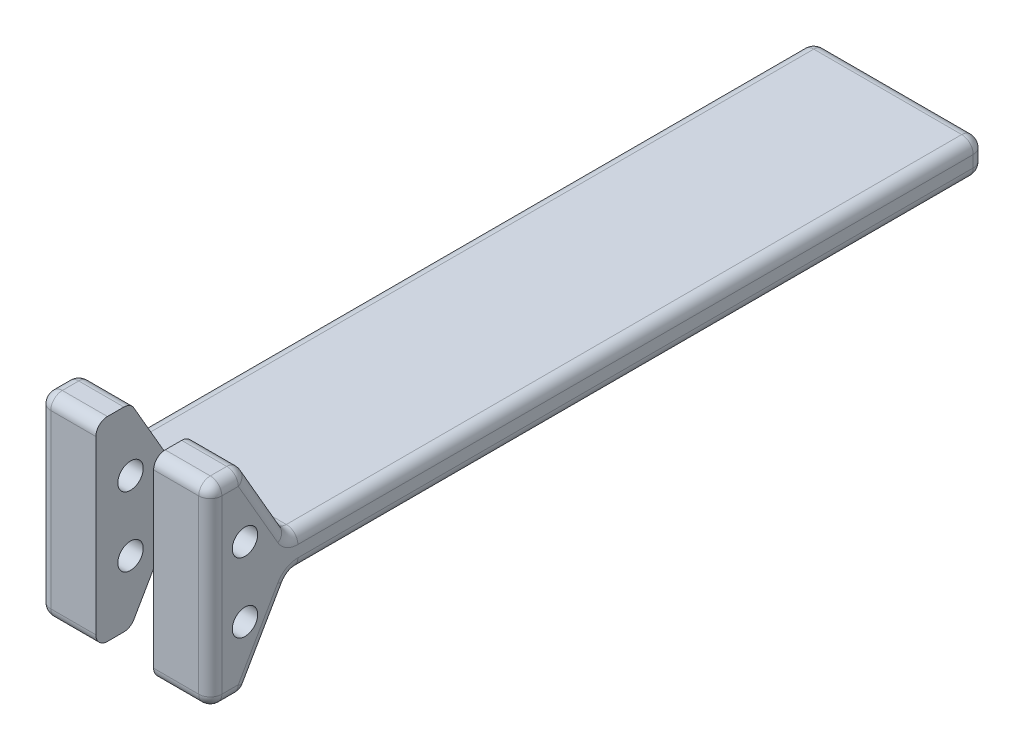
SolidWorks part; units mm, degrees
material "PLA"
ref_plane "Front Plane" through (0, 0, 0) normal (0, 0, 1) x (1, 0, 0)
ref_plane "Top Plane" through (0, 0, 0) normal (0, 1, 0) x (1, 0, 0)
ref_plane "Right Plane" through (0, 0, 0) normal (1, 0, 0) x (0, 0, -1)
sketch "Эскиз1" plane through (0, 0, 0) normal (0, 0, 1) x (1, 0, 0)
  line L9 (-7.4, 1.5) -> (7.4, 1.5)
  line L10 (-7.4, 1.5) -> (-7.4, -1.5)
  line L11 (-7.4, -1.5) -> (7.4, -1.5)
  line L12 (7.4, 1.5) -> (7.4, -1.5)
  line L13 (-7.4, 1.5) -> (7.4, -1.5) construction
  line L14 (-7.4, -1.5) -> (7.4, 1.5) construction
  point P0 (0, 0)
  dimension "D1" = 14.8
  dimension "D2" = 3
extrude "Бобышка-Вытянуть1" add sketch "Эскиз1" along normal mid plane 60
sketch "Эскиз3" plane through (0, 0, 0) normal (1, 0, 0) x (0, 0, -1)
  line L0 (-30, 1.5) -> (-34, 8.4282)
  line L5 (-34, 8.4282) -> (-37, 8.4282)
  line L6 (-37, 8.4282) -> (-37, -8.4282)
  line L7 (0, 0) -> (-35.0285, 0) construction
  line L8 (-30, -1.5) -> (-34, -8.4282)
  line L9 (-34, -8.4282) -> (-37, -8.4282)
  line L10 (-30, -1.5) -> (-30, 1.5) construction
  line L11 (-30, -1.5) -> (-30, 1.5)
  point P12 (-37, 0)
  dimension "D1" = 3
  dimension "D2" = 7
  dimension "D3" = 30
extrude "Бобышка-Вытянуть2" add sketch "Эскиз3" along normal up to surface (7.4 mm away) from offset 2.5 up to face at (7.4, 0, 0)
extrude "Бобышка-Вытянуть3" add sketch "Эскиз3<2>" against normal up to surface (7.4 mm away) from offset 2.5 up to face at (-7.4, 0, 0) offset against normal yes
sketch "Эскиз3<2>" plane through (0, 0, 0) normal (1, 0, 0) x (0, 0, -1) same geometry as "Эскиз3"
fillet "Скругление1" radius 1 30 edges at (0, 1.5, -30) (0, -1.5, -30) (-7.4, 1.5, 0) (-7.4, 4.9641, 32) (-7.4, 8.4282, 35.5) (-7.4, 0, 37) (-7.4, -8.4282, 35.5) (-7.4, -4.9641, 32) (-7.4, -1.5, 0) (-7.4, 0, -30) (7.4, -1.5, 0) (7.4, -4.9641, 32) (7.4, -8.4282, 35.5) (7.4, 0, 37) (7.4, 8.4282, 35.5) (7.4, 4.9641, 32) (7.4, 1.5, 0) (7.4, 0, -30) (-4.95, -1.5, 30) (4.95, -1.5, 30) (-4.95, 1.5, 30) (4.95, 1.5, 30) (4.95, 8.4282, 37) (-4.95, 8.4282, 37) (4.95, -8.4282, 34) (4.95, -8.4282, 37) (-4.95, -8.4282, 34) (-4.95, -8.4282, 37) (4.95, 8.4282, 34) (-4.95, 8.4282, 34)
sketch "Эскиз4" plane through (-7.4, 0, 0) normal (-1, 0, 0) x (0, 0, 1)
  line L3 (37, 0) -> (20.6591, 0) construction
  line L4 (37, 7.4282) -> (37, -7.4282) construction
  circle A0 centre (34, 3) radius 1.1
  circle A2 centre (34, -3) radius 1.1
  dimension "D1" = 2.2
  dimension "D2" = 3
  dimension "D3" = 3
extrude "Вырез-Вытянуть1" cut sketch "Эскиз4" against normal through all both and the other way through all
